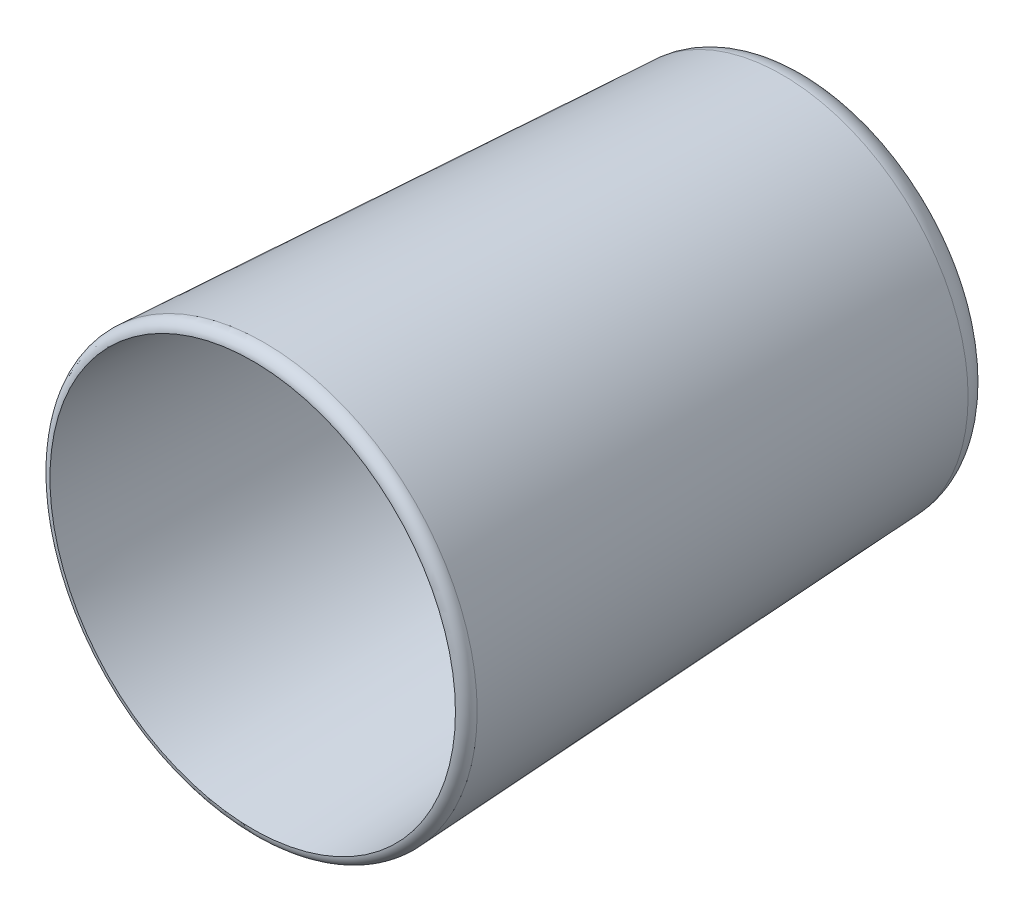
SolidWorks part; units mm, degrees
ref_plane "Plan de face" through (0, 0, 0) normal (0, 0, 1) x (1, 0, 0)
ref_plane "Plan de dessus" through (0, 0, 0) normal (0, 1, 0) x (1, 0, 0)
ref_plane "Plan de droite" through (0, 0, 0) normal (1, 0, 0) x (0, 0, -1)
sketch "Esquisse1" plane through (0, 0, 0) normal (0, 0, 1) x (1, 0, 0)
  circle A1 centre (0, 0) radius 32
  dimension "D1" = 64
extrude "Boss.-Extru.1" add sketch "Esquisse1" along normal blind 100 draft 3 draft outward yes
shell "Coque3" thickness 2 removed face at (37.2408, 0, 100) outward yes
fillet "Congé6" radius 5 1 edges at (33.8979, 0, -2)
sketch "Esquisse3" plane through (0, 0, 0) normal (0, 1, 0) x (1, 0, 0)
  line L0 (-39.2435, -100) -> (-39.1911, -99)
  line L5 (-34.1463, -2.7383) -> (-39.2435, -100) construction
  line L6 (-39.1911, -99) -> (-40.3435, -99)
  line L7 (-40.7435, -99.4) -> (-40.7435, -99.6)
  line L8 (-40.3435, -100) -> (-39.2435, -100)
  arc A0 (-40.7435, -99.6) -> (-40.3435, -100) centre (-40.3435, -99.6) ccw
  arc A1 (-40.3435, -99) -> (-40.7435, -99.4) centre (-40.3435, -99.4) ccw
  point P10 (-40.7435, -100)
  point P13 (-40.7435, -99)
  dimension "D3" = 0.4
  dimension "D1" = 1.5
  dimension "D2" = 1
fillet "Congé7" radius 2 1 edges at (39.2435, 0, 100)
